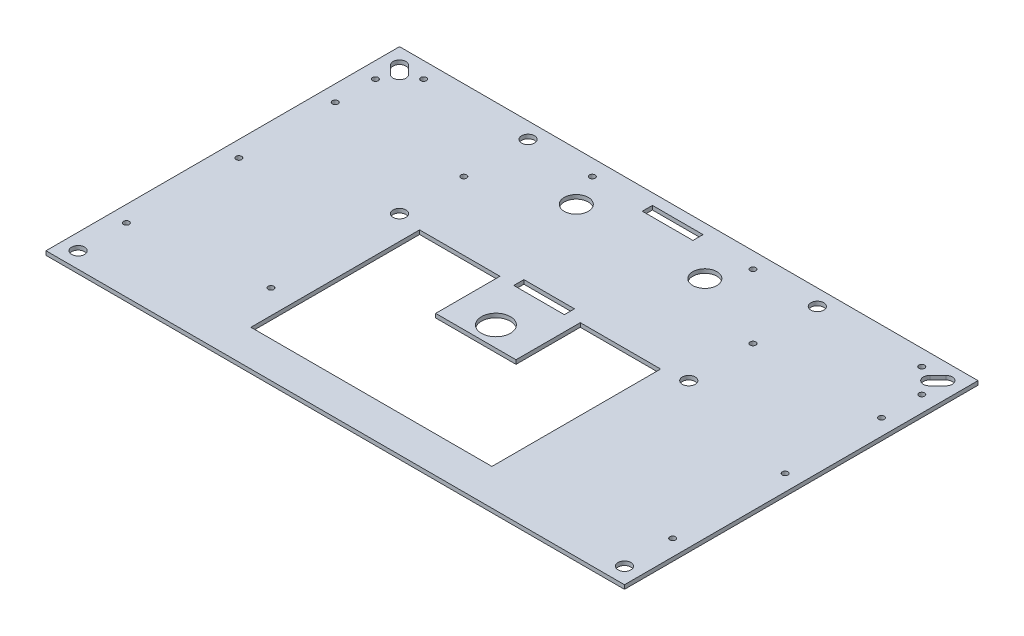
SolidWorks part; units mm, degrees
ref_plane "Front Plane" through (0, 0, 0) normal (0, 0, 1) x (1, 0, 0)
ref_plane "Top Plane" through (0, 0, 0) normal (0, 1, 0) x (1, 0, 0)
ref_plane "Right Plane" through (0, 0, 0) normal (1, 0, 0) x (0, 0, -1)
sketch "Sketch1" plane through (0, 0, 0) normal (0, 1, 0) x (1, 0, 0)
  line L1 (228.6, -139.7) -> (-228.6, -139.7)
  line L2 (228.6, -139.7) -> (228.6, 139.7)
  line L3 (228.6, 139.7) -> (-228.6, 139.7)
  line L4 (-228.6, -139.7) -> (-228.6, 139.7)
  line L5 (228.6, -139.7) -> (-228.6, 139.7) construction
  line L6 (228.6, 139.7) -> (-228.6, -139.7) construction
  point P0 (0, 0)
  dimension "D1" = 279.4
  dimension "D2" = 457.2
extrude "Boss-Extrude1" add sketch "Sketch1" along normal blind 3.175
sketch "Sketch2" plane through (0, 3.175, 0) normal (0, 1, 0) x (1, 0, 0)
  line L0 (-228.6, 139.7) -> (-228.6, -139.7) construction
  line L1 (228.6, 139.7) -> (-228.6, 139.7) construction
  line L2 (0, 0) -> (0, 139.7) construction
  line L3 (-212.3079, 130.5921) -> (-205.9579, 124.2421)
  line L4 (-219.4921, 123.4079) -> (-213.1421, 117.0579)
  line L5 (212.3079, 130.5921) -> (205.9579, 124.2421)
  line L6 (219.4921, 123.4079) -> (213.1421, 117.0579)
  line L9 (-20, 131) -> (-12, 131)
  line L10 (-20, 131) -> (-20, 123)
  line L11 (-20, 123) -> (-12, 123)
  line L12 (-12, 131) -> (-12, 123)
  line L13 (12, 131) -> (12, 123)
  line L14 (20, 123) -> (12, 123)
  line L15 (20, 131) -> (20, 123)
  line L16 (20, 131) -> (12, 131)
  line L17 (0, 76.2) -> (228.6, 76.2) construction
  line L18 (228.6, -139.7) -> (228.6, 139.7) construction
  line L19 (20, 21.4) -> (12, 21.4)
  line L20 (20, 21.4) -> (20, 29.4)
  line L21 (20, 29.4) -> (12, 29.4)
  line L22 (12, 21.4) -> (12, 29.4)
  line L23 (-12, 21.4) -> (-12, 29.4)
  line L24 (-20, 29.4) -> (-12, 29.4)
  line L25 (-20, 21.4) -> (-20, 29.4)
  line L26 (-20, 21.4) -> (-12, 21.4)
  circle A0 centre (-215.9, 127) radius 2.5 construction
  circle A1 centre (-209.55, 120.65) radius 2.5 construction
  arc A3 (-212.3079, 130.5921) -> (-219.4921, 123.4079) centre (-215.9, 127) ccw
  arc A4 (-213.1421, 117.0579) -> (-205.9579, 124.2421) centre (-209.55, 120.65) ccw
  arc A5 (213.1421, 117.0579) -> (205.9579, 124.2421) centre (209.55, 120.65) cw
  arc A6 (212.3079, 130.5921) -> (219.4921, 123.4079) centre (215.9, 127) cw
  circle A7 centre (-114.3, 127) radius 5.08
  circle A8 centre (114.3, 127) radius 5.08
  circle A9 centre (-215.9, -127) radius 5.08
  circle A10 centre (215.9, -127) radius 5.08
  circle A11 centre (114.3, 25.4) radius 5.08
  circle A12 centre (-114.3, 25.4) radius 5.08
  circle A13 centre (0, -12.7) radius 11.43
  point P32 (-20, 127)
  point P33 (-16, 131)
  point P38 (16, 131)
  point P39 (20, 127)
  point P56 (20, 25.4)
  point P57 (16, 21.4)
  point P58 (-16, 21.4)
  point P59 (-20, 25.4)
  dimension "D1" = 5
  dimension "D6" = 10.16
  dimension "D13" = 22.86
  dimension "D2" = 12.7
  dimension "D3" = 12.7
  dimension "D4" = 19.05
  dimension "D5" = 19.05
  dimension "D7" = 101.6
  dimension "D8" = 254
  dimension "D9" = 8
  dimension "D10" = 12.7
  dimension "D11" = 16
  dimension "D14" = 12.7
  dimension "D12" = 50.8
extrude "Cut-Extrude1" cut sketch "Sketch2" against normal blind 3.175
sketch "Sketch3" plane through (0, 3.175, 0) normal (0, 1, 0) x (1, 0, 0)
  line L1 (-20, 131) -> (20, 131)
  line L2 (-20, 131) -> (-20, 123)
  line L3 (-20, 123) -> (20, 123)
  line L4 (20, 131) -> (20, 123)
  line L5 (-20, 29.4) -> (20, 29.4)
  line L6 (-20, 29.4) -> (-20, 21.4)
  line L7 (-20, 21.4) -> (20, 21.4)
  line L8 (20, 29.4) -> (20, 21.4)
extrude "Cut-Extrude2" cut sketch "Sketch3" against normal blind 25.4
sketch "Sketch4" plane through (0, 3.175, 0) normal (0, 1, 0) x (1, 0, 0)
  line L0 (0, 0) -> (0, 139.7) construction
  line L1 (228.6, 139.7) -> (-228.6, 139.7) construction
  line L2 (-228.6, 139.7) -> (-228.6, -139.7) construction
  circle A0 centre (-196.85, 127) radius 2.25
  circle A1 centre (-215.9, 107.95) radius 2.25
  circle A2 centre (196.85, 127) radius 2.25
  circle A3 centre (215.9, 107.95) radius 2.25
  dimension "D3" = 4.5
  dimension "D1" = 12.7
  dimension "D2" = 31.75
  dimension "D4" = 12.7
  dimension "D5" = 31.75
extrude "Cut-Extrude3" cut sketch "Sketch4" against normal blind 25.4
sketch "Sketch5" plane through (0, 3.175, 0) normal (0, 1, 0) x (1, 0, 0)
  line L0 (228.6, 139.7) -> (-228.6, 139.7) construction
  line L1 (0, 139.7) -> (0, 29.4) construction
  line L2 (20, 29.4) -> (-20, 29.4) construction
  circle A0 centre (-50.8, 101.6) radius 9.525
  circle A1 centre (50.8, 101.6) radius 9.525
  dimension "D1" = 19.05
  dimension "D3" = 50.8
  dimension "D2" = 38.1
extrude "Cut-Extrude4" cut sketch "Sketch5" against normal blind 101.6
sketch "Sketch6" plane through (0, 3.175, 0) normal (0, 1, 0) x (1, 0, 0)
  line L0 (0, 139.7) -> (0, -139.7) construction
  line L1 (228.6, 139.7) -> (-228.6, 139.7) construction
  line L2 (-228.6, -139.7) -> (228.6, -139.7) construction
  line L3 (-228.6, 139.7) -> (-228.6, -139.7) construction
  line L4 (-114.3, 132.08) -> (-114.3, -139.7) construction
  circle A0 centre (-215.9, 76.2) radius 2.25
  circle A1 centre (-215.9, 0) radius 2.25
  circle A2 centre (-215.9, -88.9) radius 2.25
  circle A7 centre (-114.3, 127) radius 5.08 construction
  circle A8 centre (-114.3, -76.2) radius 2.25
  circle A10 centre (-114.3, 76.2) radius 2.25
  circle A11 centre (-63.5, 127) radius 2.25
  circle A12 centre (63.5, 127) radius 2.25
  circle A13 centre (114.3, 76.2) radius 2.25
  circle A14 centre (215.9, -88.9) radius 2.25
  circle A15 centre (215.9, 0) radius 2.25
  circle A16 centre (215.9, 76.2) radius 2.25
  dimension "D1" = 4.5
  dimension "D2" = 4.5
  dimension "D3" = 4.5
  dimension "D7" = 4.5
  dimension "D8" = 4.5
  dimension "D9" = 4.5
  dimension "D10" = 63.5
  dimension "D11" = 63.5
  dimension "D4" = 12.7
  dimension "D5" = 12.7
  dimension "D6" = 12.7
  dimension "D12" = 12.7
  dimension "D13" = 50.8
  dimension "D14" = 139.7
  dimension "D15" = 63.5
  dimension "D16" = 63.5
extrude "Cut-Extrude5" cut sketch "Sketch6" against normal blind 637.032
sketch "Sketch7" plane through (0, 3.175, 0) normal (0, 1, 0) x (1, 0, 0)
  line L1 (95.25, -111.125) -> (-95.25, -111.125)
  line L2 (95.25, -111.125) -> (95.25, -28.575)
  line L3 (95.25, -28.575) -> (-95.25, -28.575)
  line L4 (-95.25, -111.125) -> (-95.25, -28.575)
  line L5 (95.25, -111.125) -> (-95.25, -28.575) construction
  line L6 (95.25, -28.575) -> (-95.25, -111.125) construction
  line L7 (-95.25, -28.575) -> (-31.75, -28.575)
  line L8 (-95.25, -28.575) -> (-95.25, 22.225)
  line L9 (-95.25, 22.225) -> (-31.75, 22.225)
  line L10 (-31.75, -28.575) -> (-31.75, 22.225)
  line L11 (95.25, -28.575) -> (31.75, -28.575)
  line L12 (95.25, -28.575) -> (95.25, 22.225)
  line L13 (95.25, 22.225) -> (31.75, 22.225)
  line L14 (31.75, -28.575) -> (31.75, 22.225)
  point P0 (0, -69.85)
  dimension "D1" = 190.5
  dimension "D2" = 69.85
  dimension "D3" = 82.55
  dimension "D4" = 50.8
  dimension "D5" = 63.5
extrude "Cut-Extrude6" cut sketch "Sketch7" against normal blind 25.4 contours L4 L1 L2 L3 | L3 L10 L9 L8 | L14 L3 L12 L13 region at (0, 3.175, 69.85) region at (63.5, 3.175, 3.175) region at (-63.5, 3.175, 3.175)
